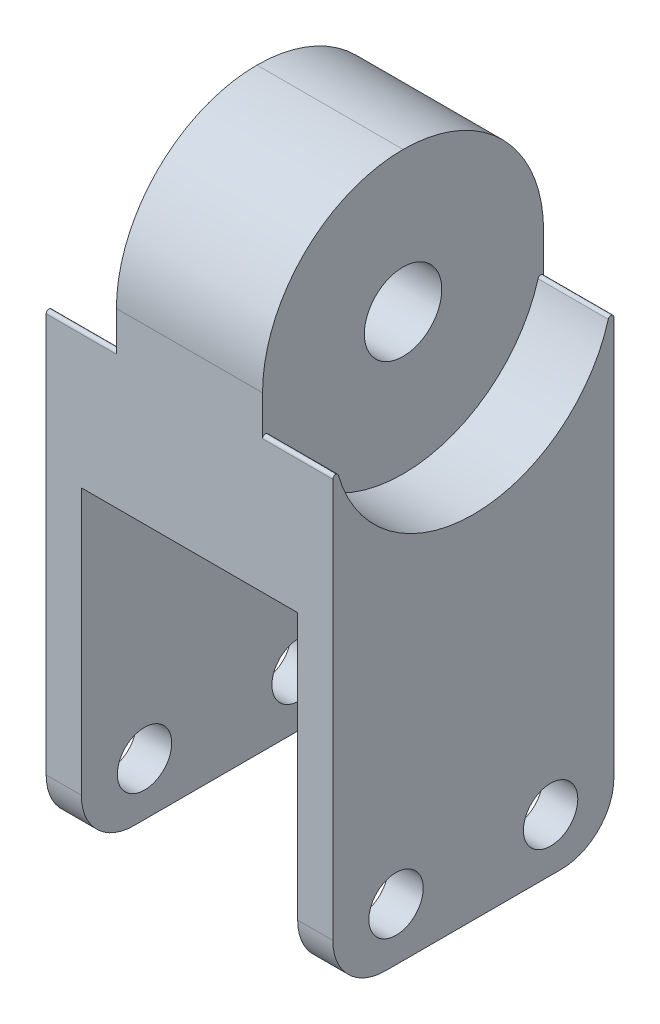
SolidWorks part; units mm, degrees
ref_plane "Front Plane" through (0, 0, 0) normal (0, 0, 1) x (1, 0, 0)
ref_plane "Top Plane" through (0, 0, 0) normal (0, 1, 0) x (1, 0, 0)
ref_plane "Right Plane" through (0, 0, 0) normal (1, 0, 0) x (0, 0, -1)
sketch "Sketch6" plane through (0, 0, 0) normal (0, 0, 1) x (1, 0, 0)
  line L1 (-9.525, 9.525) -> (9.525, 9.525)
  line L2 (-9.525, 9.525) -> (-9.525, -9.525)
  line L3 (-9.525, -9.525) -> (9.525, -9.525)
  line L4 (9.525, 9.525) -> (9.525, -9.525)
  line L5 (-9.525, 9.525) -> (9.525, -9.525) construction
  line L6 (-9.525, -9.525) -> (9.525, 9.525) construction
  point P0 (0, 0)
  dimension "D1" = 19.05
sketch "Sketch7" plane through (0, 0, 0) normal (0, 0, 1) x (1, 0, 0)
  line L1 (-12.954, -19.05) -> (-12.954, 12.954)
  line L7 (12.954, 12.954) -> (12.954, -19.05)
  line L8 (12.954, -19.05) -> (9.779, -19.05)
  line L9 (9.779, -19.05) -> (9.779, 9.779)
  line L11 (-9.779, 9.779) -> (-9.779, -19.05)
  line L12 (-9.779, -19.05) -> (-12.954, -19.05)
  line L14 (-9.779, 9.779) -> (9.779, 9.779)
  line L15 (-9.525, 9.525) -> (9.525, 9.525) construction
  line L16 (9.525, 9.525) -> (9.525, -9.525) construction
  line L17 (-9.525, -9.525) -> (9.525, -9.525) construction
  line L18 (-12.954, 12.954) -> (-6.604, 12.954)
  line L19 (-6.604, 12.954) -> (-6.604, 38.1)
  line L20 (-6.604, 38.1) -> (6.604, 38.1)
  line L21 (6.604, 38.1) -> (6.604, 12.954)
  line L22 (6.604, 12.954) -> (12.954, 12.954)
  point P13 (0, 9.779)
  dimension "D1" = 0.254
  dimension "D2" = 0.254
  dimension "D3" = 3.175
  dimension "D7" = 9.525
  dimension "D4" = 3.175
  dimension "D5" = 6.35
  dimension "D6" = 38.1
extrude "Boss-Extrude4" add sketch "Sketch7" along normal mid plane 25.4
hole_wizard "#8 Clearance Hole1" positions "Sketch8" profile "Sketch9" hole size "#8" standard "ANSI Inch" end condition through all
sketch "Sketch8" plane through (12.954, 0, 0) normal (1, 0, 0) x (0, 0, -1)
  line L0 (-6.985, -14.2875) -> (6.985, -14.2875)
  line L2 (-12.7, -19.05) -> (12.7, -19.05) construction
  point P0 (-6.985, -14.2875)
  point P2 (6.985, -14.2875)
  point P9 (0, -14.2875)
  dimension "D1" = 13.97
  dimension "D2" = 4.7625
sketch "Sketch9" plane through (12.954, -14.2875, 6.985) normal (0, 1, 0) x (0, 0, -1)
  line L0 (0, 0) -> (0, 25.908)
  line L1 (0, 25.908) -> (2.4574, 25.908)
  line L2 (2.4574, 25.908) -> (2.4574, 0)
  line L5 (2.4574, 0) -> (0, 0)
  line L11 (0, -6.35) -> (0, 107.95) construction
  dimension "Thru Hole Dia." = 4.9149
  dimension "Thru Hole Depth" = 25.908
fillet "Fillet2" radius 4.7625 4 edges at (-11.3665, -19.05, 12.7) (-11.3665, -19.05, -12.7) (11.3665, -19.05, -12.7) (11.3665, -19.05, 12.7)
fillet "Fillet3" radius 12.7 2 edges at (0, 38.1, 12.7) (0, 38.1, -12.7)
hole_wizard "M6 Clearance Hole2" positions "Sketch10" profile "Sketch11" hole size "M6" standard "ANSI Metric" end condition through all
sketch "Sketch10" plane through (-6.604, 0, 0) normal (1, 0, 0) x (0, 0, -1)
  arc A1 (12.7, 25.4) -> (0, 38.1) centre (0, 25.4) ccw construction
  point P0 (0, 25.4)
sketch "Sketch11" plane through (-6.604, 25.4, 0) normal (0, 1, 0) x (0, 0, 1)
  line L0 (0, 0) -> (0, 19.558)
  line L1 (0, 19.558) -> (3.5, 19.558)
  line L2 (3.5, 19.558) -> (3.5, 0)
  line L5 (3.5, 0) -> (0, 0)
  line L11 (0, -6.35) -> (0, 107.95) construction
  dimension "Thru Hole Dia." = 7
  dimension "Thru Hole Depth" = 19.558
sketch "Sketch12" plane through (6.604, 0, 0) normal (1, 0, 0) x (0, 0, -1)
  line L0 (-12.7, 12.954) -> (-12.7, 25.4) construction
  line L1 (-12.7, 12.954) -> (12.7, 12.954) construction
  line L2 (12.7, 12.954) -> (12.7, 25.4) construction
  line L3 (-12.7, 12.954) -> (-12.7, 21.8079)
  line L4 (-12.7, 12.954) -> (-2.5273, 12.954)
  line L5 (12.7, 12.954) -> (12.7, 21.8079)
  line L6 (-2.5273, 12.954) -> (2.5273, 12.954) construction
  line L7 (2.5273, 12.954) -> (12.7, 12.954)
  arc A0 (2.5273, 12.954) -> (12.202, 21.8783) centre (0, 25.4) ccw
  arc A1 (0, 38.1) -> (-12.7, 25.4) centre (0, 25.4) ccw construction
  arc A2 (-2.5273, 12.954) -> (2.5273, 12.954) centre (0, 25.4) ccw construction
  arc A3 (12.7, 25.4) -> (-12.7, 25.4) centre (0, 25.4) ccw construction
  arc A4 (-12.202, 21.8783) -> (-2.5273, 12.954) centre (0, 25.4) ccw
  arc A5 (12.7, 21.8079) -> (12.202, 21.8783) centre (12.446, 21.8079) ccw
  arc A6 (-12.7, 21.8079) -> (-12.202, 21.8783) centre (-12.446, 21.8079) cw
  dimension "D1" = 0.254
extrude "Boss-Extrude5" add sketch "Sketch12" along normal up to surface (6.35 mm away) from surface up to face at (12.954, -14.2875, 4.5276) starting at face at (-12.954, -14.2875, 4.5276)
sketch "Sketch13" plane through (12.954, 0, 0) normal (1, 0, 0) x (0, 0, -1)
  line L0 (-2.5273, 12.954) -> (2.5273, 12.954) construction
  line L1 (-2.5273, 12.954) -> (2.5273, 12.954)
  arc A0 (-2.5273, 12.954) -> (2.5273, 12.954) centre (0, 25.4) ccw
  arc A1 (12.7, 25.4) -> (0, 38.1) centre (0, 25.4) ccw construction
  arc A2 (2.5273, 12.954) -> (-2.5273, 12.954) centre (0, 25.4) ccw construction
extrude "Cut-Extrude1" cut sketch "Sketch13" against normal up to surface (6.35 mm away) up to face at (6.604, 22.7968, 0)
extrude "Cut-Extrude2" cut sketch "Sketch13<2>" along direction (1, 0, 0) on the side against the normal up to surface (25.908 mm away) from surface up to face at (-12.954, -14.2875, 4.5276) starting at face at (-6.604, 22.7968, 0)
sketch "Sketch13<2>" plane through (12.954, 0, 0) normal (1, 0, 0) x (0, 0, -1) same geometry as "Sketch13"
equation "\"tol\"=0.01"
equation "\"D1@Sketch7\"=\"tol\""
equation "\"D2@Sketch7\"=\"tol\""
